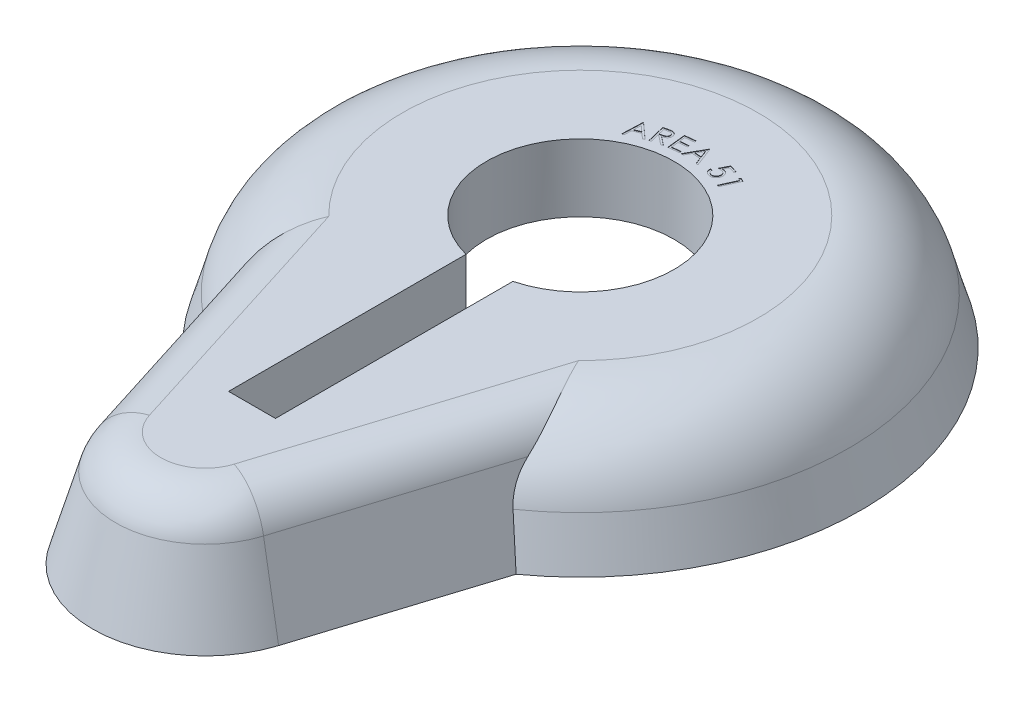
SolidWorks part; units mm, degrees
material "Brass"
ref_plane "Front Plane" through (0, 0, 0) normal (0, 0, 1) x (1, 0, 0)
ref_plane "Top Plane" through (0, 0, 0) normal (0, 1, 0) x (1, 0, 0)
ref_plane "Right Plane" through (0, 0, 0) normal (1, 0, 0) x (0, 0, -1)
sketch "Sketch1" plane through (0, 0, 0) normal (0, 1, 0) x (1, 0, 0)
  line L0 (0, 0) -> (0, 456.3925) construction
  line L1 (-572.2302, -180.4235) -> (-875.7383, 782.1813)
  line L2 (572.2302, -180.4235) -> (875.7383, 782.1813)
  arc A0 (-572.2302, -180.4235) -> (572.2302, -180.4235) centre (0, 0) ccw
  arc A1 (-875.7383, 782.1813) -> (875.7383, 782.1813) centre (0, 2000) cw
  dimension "D1" = 600
  dimension "D2" = 1500
  dimension "D3" = 2000
  dimension "D4" = 35
extrude "Boss-Extrude1" add sketch "Sketch1" along normal blind 610 draft 16
fillet "Fillet1" radius 250 3 edges at (566.2115, 610, -382.1683) (0, 610, 425.0853) (-566.2115, 610, -382.1683)
fillet "Fillet2" radius 500 1 edges at (0, 610, -3325.0853)
sketch "Sketch2" plane through (0, 0, 0) normal (0, -1, 0) x (1, 0, 0)
  line L4 (-476.8585, 150.3529) -> (-790.5561, -844.5689)
  line L5 (790.5561, -844.5689) -> (476.8585, 150.3529)
  line L6 (-476.8585, 150.3529) -> (-790.5561, -844.5689)
  line L7 (790.5561, -844.5689) -> (476.8585, 150.3529)
  arc A4 (476.8585, 150.3529) -> (-476.8585, 150.3529) centre (0, 0) ccw
  arc A5 (-790.5561, -844.5689) -> (790.5561, -844.5689) centre (0, -2000) ccw
  arc A6 (476.8585, 150.3529) -> (-476.8585, 150.3529) centre (0, 0) ccw
  arc A7 (-790.5561, -844.5689) -> (790.5561, -844.5689) centre (0, -2000) ccw
  dimension "D1" = 100
extrude "Cut-Extrude1" cut sketch "Sketch2" against normal blind 250 draft 16
sketch "Sketch3" plane through (0, 610, 0) normal (0, 1, 0) x (1, 0, 0)
  circle A0 centre (0, 2000) radius 500
  dimension "D1" = 1000
extrude "Cut-Extrude2" cut sketch "Sketch3" against normal through all
sketch "Sketch4" plane through (0, 610, 0) normal (0, 1, 0) x (1, 0, 0)
  line L0 (0, 250) -> (0, 0) construction
  line L2 (-125, 2250) -> (125, 2250)
  line L3 (-125, 2250) -> (-125, 250)
  line L4 (-125, 250) -> (125, 250)
  line L5 (125, 2250) -> (125, 250)
  point P6 (0, 0)
  dimension "D1" = 250
  dimension "D2" = 250
  dimension "D3" = 2000
extrude "Cut-Extrude3" cut sketch "Sketch4" against normal blind 250
sketch "Sketch5" plane through (0, 610, 0) normal (0, 1, 0) x (1, 0, 0)
  arc A0 (-500, 2240.2752) -> (500, 2240.2752) centre (0, 2000) cw construction
  text T0 "AREA 51" font "Century Gothic" height 100
  point P4 (0, 0)
extrude "Cut-Extrude4" cut sketch "Sketch5" against normal blind 2
